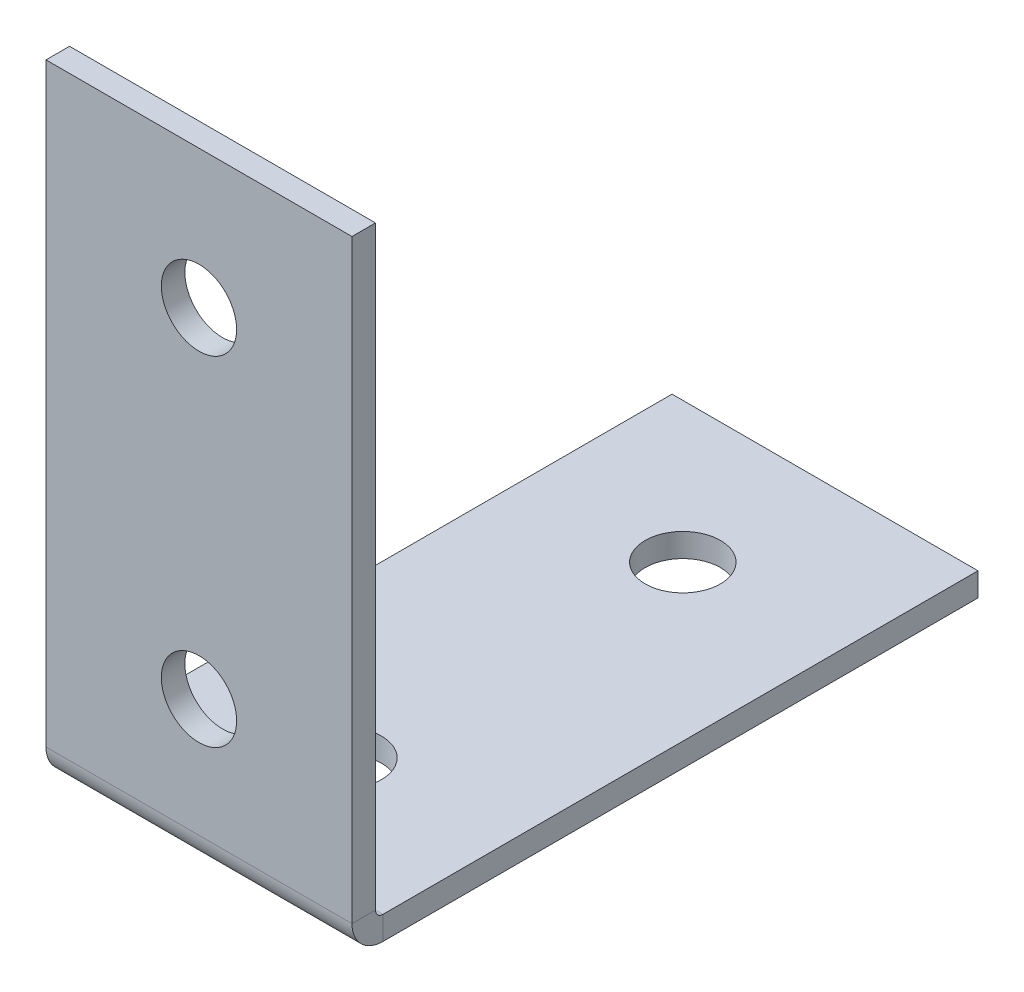
SolidWorks part; units mm, degrees
note: The reader was unsure of these and kept them because the rebuilt part matched: flange length of "Edge-Flange1".
ref_plane "Front Plane" through (0, 0, 0) normal (0, 0, 1) x (1, 0, 0)
ref_plane "Top Plane" through (0, 0, 0) normal (0, 1, 0) x (1, 0, 0)
ref_plane "Right Plane" through (0, 0, 0) normal (1, 0, 0) x (0, 0, -1)
sketch "Sketch2" plane through (0, 0, 0) normal (0, 1, 0) x (1, 0, 0)
  line L1 (0, 0) -> (41.275, 0)
  line L2 (0, 0) -> (0, 81.28)
  line L3 (0, 81.28) -> (41.275, 81.28)
  line L4 (41.275, 0) -> (41.275, 81.28)
  dimension "D1" = 81.28
  dimension "D2" = 41.275
base flange "Base-Flange1" sketch "Sketch2" thickness 3.175 reverse thickness direction no parameters "D1"=1
edge flange "Edge-Flange1" sketch "Sketch9" flange angle 90 flange length 81.28 flange position material outside bend radius 1 thickness 3.175 relief rectangular parameters "D6"=10
sketch "Sketch9" plane through (0, 0, 0) normal (0, 0, 1) x (1, 0, 0)
  line L2 (0, 0) -> (0, 81.28)
  line L3 (0, 81.28) -> (41.275, 81.28)
  line L4 (41.275, 81.28) -> (41.275, 0)
  line L7 (0, 0) -> (41.275, 0) construction
  line L8 (0, 0) -> (41.275, 0)
bend "EdgeBend1" bend radius 1 bend angle 90 parameters "D5"=1
sketch "Sketch10" plane through (0, 0, 0) normal (0, 0, -1) x (-1, 0, 0)
  line L0 (-41.275, 81.28) -> (0, 81.28) construction
  circle A0 centre (-20.6375, 62.6387) radius 5.08
  circle A1 centre (-20.6375, 16.9187) radius 5.08
  point P4 (0, 0)
  point P7 (-20.6375, 81.28)
  point P8 (0, 0)
  dimension "D1" = 10.16
  dimension "D2" = 45.72
extrude "Cut-Extrude1" cut sketch "Sketch10" against normal up to next normal cut yes
sketch "Sketch12" plane through (0, 0, 0) normal (0, 1, 0) x (1, 0, 0)
  circle A0 centre (20.3598, 16.6546) radius 5.08
  circle A1 centre (20.36, 62.3746) radius 5.08
  point P4 (0, 0)
  point P7 (20.36, 16.6546)
  dimension "D1" = 10.16
  dimension "D2" = 45.72
extrude "Cut-Extrude3" cut sketch "Sketch12" against normal up to next normal cut yes
sketch "Bend-Lines1" [suppressed] plane through (0, 0, 0) normal (0, 1, 0) x (1, 0, 0)
sketch "Bounding-Box1" [suppressed] plane through (0, 0, 0) normal (0, 1, 0) x (1, 0, 0)
sheet metal parameters "Sheet-Metal1" thickness 3.175 parameters "D1"=1
flat pattern "Flat-Pattern1" [suppressed]
sketch "Bend-Lines2" plane through (0, 0, 0) normal (0, 1, 0) x (1, 0, 0)
sketch3d "Bounding-Box2" [suppressed]
  line L0 (0, 0, 0) -> (0, 81.28, 0) construction
  line L1 (-41.275, 0, 0) -> (-41.275, 81.28, 0) construction
  line L2 (0, 0, 0) -> (-41.275, 0, 0) construction
  line L3 (0, 81.28, 0) -> (-41.275, 81.28, 0) construction
sheet metal parameters "Sheet-Metal2" thickness 3.175 parameters "D1"=1
flat pattern "Flat-Pattern1"
sketch "Bend-Lines2" plane through (0, 0, 0) normal (0, 1, 0) x (1, 0, 0)
  line L0 (0, 0.2146) -> (41.275, 0.2146) construction
  line L1 (0, 0.2146) -> (41.275, 0.2146) construction
sketch3d "Bounding-Box2" [suppressed]
  line L0 (0, -80.8508, 0) -> (0, 81.28, 0) construction
  line L1 (41.275, -80.8508, 0) -> (41.275, 81.28, 0) construction
  line L2 (0, -80.8508, 0) -> (41.275, -80.8508, 0) construction
  line L3 (0, 81.28, 0) -> (41.275, 81.28, 0) construction
bend of the flat pattern "Flatten-<EdgeBend1>1"
sheet metal parameters "Sheet-Metal3" thickness 3.175 parameters "D1"=1
flat pattern "Flat-Pattern1"
sketch "Bend-Lines2" plane through (0, 0, 0) normal (0, 1, 0) x (1, 0, 0)
  line L0 (0, 0.2146) -> (41.275, 0.2146) construction
  line L1 (0, 0.2146) -> (41.275, 0.2146) construction
sketch3d "Bounding-Box2" [suppressed]
  line L0 (0, -80.8508, 0) -> (0, 81.28, 0) construction
  line L1 (41.275, -80.8508, 0) -> (41.275, 81.28, 0) construction
  line L2 (0, -80.8508, 0) -> (41.275, -80.8508, 0) construction
  line L3 (0, 81.28, 0) -> (41.275, 81.28, 0) construction
bend of the flat pattern "Flatten-<EdgeBend1>1"
sheet metal parameters "Sheet-Metal5" thickness 3.175 parameters "D1"=1
flat pattern "Flat-Pattern1"
sketch "Bend-Lines2" plane through (0, 0, 0) normal (0, 1, 0) x (1, 0, 0)
  line L0 (0, 0.2146) -> (41.275, 0.2146) construction
  line L1 (0, 0.2146) -> (41.275, 0.2146) construction
sketch3d "Bounding-Box2" [suppressed]
  line L0 (0, -80.8508, 0) -> (0, 81.28, 0) construction
  line L1 (41.275, -80.8508, 0) -> (41.275, 81.28, 0) construction
  line L2 (0, -80.8508, 0) -> (41.275, -80.8508, 0) construction
  line L3 (0, 81.28, 0) -> (41.275, 81.28, 0) construction
bend of the flat pattern "Flatten-<EdgeBend1>1"
